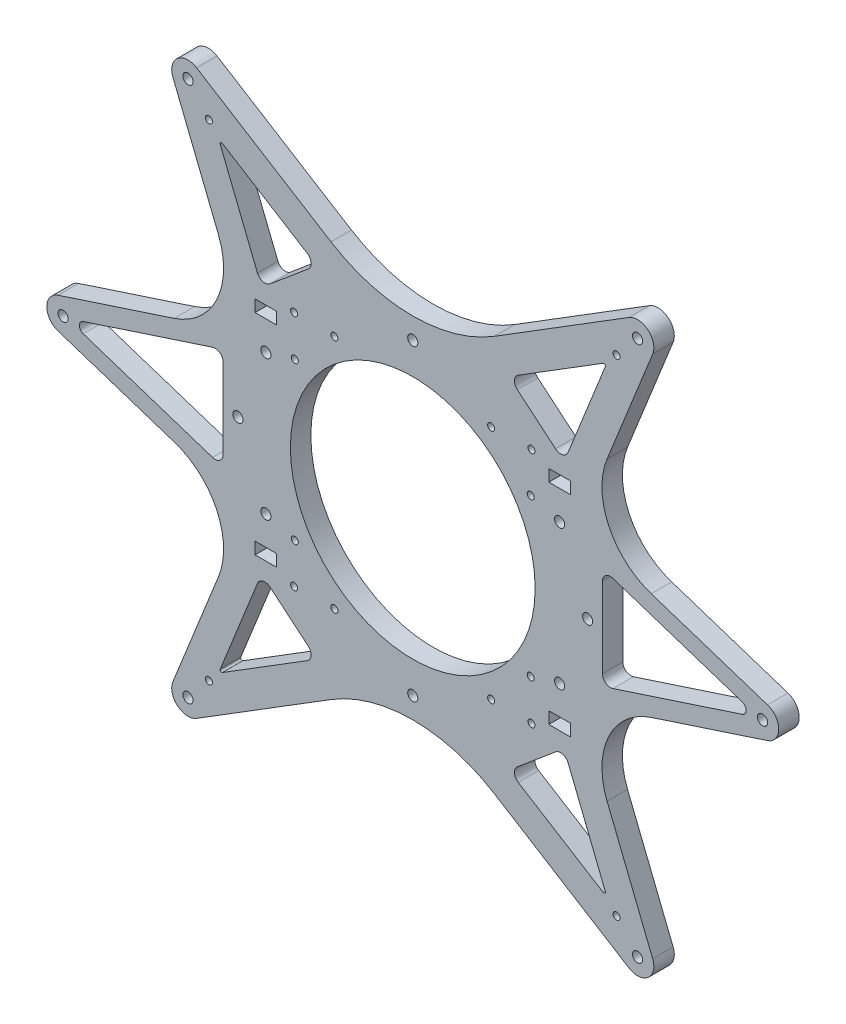
SolidWorks part; units mm, degrees
material "Acrylic (Medium-high impact)"
ref_plane "Front Plane" through (0, 0, 0) normal (0, 0, 1) x (1, 0, 0)
ref_plane "Top Plane" through (0, 0, 0) normal (0, 1, 0) x (1, 0, 0)
ref_plane "Right Plane" through (0, 0, 0) normal (1, 0, 0) x (0, 0, -1)
sketch "Sketch1" plane through (0, 0, 0) normal (0, 0, 1) x (1, 0, 0)
  line L0 (-447622.4345, 422.8828) -> (448935.6268, 422.8828) construction
  line L1 (587.9953, 497.7534) -> (601.0264, 465.2697)
  line L2 (698.5962, 452.8828) -> (698.5962, 392.8828) construction
  line L3 (653.3971, 419.0702) -> (-31485.9834, -37883.1519) construction
  line L4 (701.6962, 394.5828) -> (695.4962, 391.1828) construction
  line L5 (701.6962, 391.1828) -> (695.4962, 394.5828) construction
  line L6 (626.4541, 473.2977) -> (602.1777, 488.3841)
  line L7 (594.7755, 503.4426) -> (633.2109, 479.5572)
  line L8 (601.5396, 487.8487) -> (612.1813, 461.3214)
  line L9 (598.3082, 492.3477) -> (598.7333, 491.841) construction
  line L10 (701.6962, 391.1828) -> (695.4962, 391.1828)
  line L11 (695.4962, 394.5828) -> (695.4962, 391.1828)
  line L12 (701.6962, 394.5828) -> (695.4962, 394.5828)
  line L13 (594.7755, 503.4426) -> (587.9953, 497.7534) construction
  line L14 (626.7171, 469.6022) -> (615.775, 460.4206)
  line L15 (686.4752, 469.6022) -> (697.4174, 460.4206)
  line L16 (701.6962, 394.5828) -> (701.6962, 391.1828)
  line L17 (-343.4038, 422.8828) -> (49656.5962, 422.8828) construction
  line L18 (648.8948, 432.061) -> (-31490.4849, 38734.2822) construction
  line L19 (-347.3366, 472.8828) -> (49652.6634, 472.8828) construction
  line L20 (-347.2527, 372.8828) -> (49652.7473, 372.8828) construction
  line L21 (562.3601, 421.3552) -> (599.3601, 409.2322)
  line L22 (602.3601, 434.3594) -> (602.3601, 411.4062)
  line L23 (555.1462, 427.3082) -> (555.1462, 418.4573) construction
  line L24 (562.3601, 424.4103) -> (599.3601, 436.5334)
  line L25 (599.3601, 409.2322) -> (599.3601, 436.5334) construction
  line L26 (555.1462, 427.3082) -> (588.4064, 438.2059)
  line L27 (562.3601, 421.3552) -> (562.3601, 424.4103) construction
  line L28 (555.1462, 418.4573) -> (588.4064, 407.5596)
  line L29 (686.7382, 473.2977) -> (711.0147, 488.3841)
  line L30 (594.7755, 342.3229) -> (633.2109, 366.2084)
  line L31 (711.6527, 487.8487) -> (701.0111, 461.3214)
  line L32 (611.4962, 451.1828) -> (617.6962, 454.5828) construction
  line L33 (611.4962, 454.5828) -> (617.6962, 451.1828) construction
  line L34 (601.5396, 357.9169) -> (612.1813, 384.4442)
  line L35 (587.9953, 348.0122) -> (594.7755, 342.3229) construction
  line L36 (626.4541, 372.4678) -> (602.1777, 357.3814)
  line L37 (626.7171, 376.1634) -> (615.775, 385.3449)
  line L38 (587.9953, 348.0122) -> (601.0264, 380.4959)
  line L39 (611.4962, 391.1828) -> (617.6962, 394.5828) construction
  line L40 (701.6962, 454.5828) -> (695.4962, 451.1828) construction
  line L41 (611.4962, 394.5828) -> (617.6962, 391.1828) construction
  line L42 (614.5962, 452.8828) -> (614.5962, 392.8828) construction
  line L43 (701.6962, 451.1828) -> (695.4962, 454.5828) construction
  line L44 (686.4752, 376.1634) -> (697.4174, 385.3449)
  line L45 (725.1971, 348.0122) -> (718.4169, 342.3229) construction
  line L46 (711.6527, 357.9169) -> (701.0111, 384.4442)
  line L47 (750.8323, 421.3552) -> (750.8323, 424.4103) construction
  line L48 (713.8323, 409.2322) -> (713.8323, 436.5334) construction
  line L49 (758.0462, 427.3082) -> (758.0462, 418.4573) construction
  line L50 (686.7382, 372.4678) -> (711.0147, 357.3814)
  line L51 (718.4169, 503.4426) -> (725.1971, 497.7534) construction
  line L53 (611.4962, 454.5828) -> (617.6962, 454.5828)
  line L54 (617.6962, 451.1828) -> (617.6962, 454.5828)
  line L55 (611.4962, 451.1828) -> (617.6962, 451.1828)
  line L56 (701.6962, 451.1828) -> (701.6962, 454.5828)
  line L57 (701.6962, 451.1828) -> (695.4962, 451.1828)
  line L58 (695.4962, 451.1828) -> (695.4962, 454.5828)
  line L59 (701.6962, 454.5828) -> (695.4962, 454.5828)
  line L60 (725.1971, 348.0122) -> (712.166, 380.4959)
  line L63 (718.4169, 342.3229) -> (679.9814, 366.2084)
  line L65 (758.0462, 418.4573) -> (724.786, 407.5596)
  line L66 (758.0462, 427.3082) -> (724.786, 438.2059)
  line L67 (750.8323, 424.4103) -> (713.8323, 436.5334)
  line L68 (710.8323, 434.3594) -> (710.8323, 411.4062)
  line L69 (750.8323, 421.3552) -> (713.8323, 409.2322)
  line L70 (611.4962, 451.1828) -> (611.4962, 454.5828)
  line L72 (611.4962, 394.5828) -> (611.4962, 391.1828)
  line L73 (611.4962, 394.5828) -> (617.6962, 394.5828)
  line L74 (617.6962, 394.5828) -> (617.6962, 391.1828)
  line L76 (718.4169, 503.4426) -> (679.9814, 479.5572)
  line L78 (725.1971, 497.7534) -> (712.166, 465.2697)
  line L79 (611.4962, 391.1828) -> (617.6962, 391.1828)
  line L80 (706.5962, 432.8828) -> (698.5962, 432.8828) construction
  line L82 (656.5962, 378.8828) -> (646.5962, 378.8828) construction
  line L83 (656.5962, 466.8828) -> (646.5962, 466.8828) construction
  line L84 (-50.5106, -284.224) -> (35304.8285, 35071.1151) construction
  line L85 (-50.5106, -284.224) -> (35304.8285, 35071.1151) construction
  line L86 (1363.703, -284.224) -> (-33991.6361, 35071.1151) construction
  line L91 (598.3082, 492.3477) -> (595.2884, 495.9465) construction
  line L92 (592.3174, 499.4872) -> (598.3082, 492.3477) construction
  line L111 (656.5962, -513.6368) -> (656.5962, 49486.3632) construction
  arc A0 (601.5396, 487.8487) -> (602.1777, 488.3841) centre (601.9464, 488.0119) cw
  arc A1 (587.9953, 497.7534) -> (594.7755, 503.4426) centre (592.3174, 499.4872) cw
  circle A2 centre (592.3174, 499.4872) radius 1.45
  arc A4 (612.1813, 461.3214) -> (615.775, 460.4206) centre (614.3045, 462.1731) ccw
  arc A5 (626.4541, 473.2977) -> (626.7171, 469.6022) centre (625.2466, 471.3546) cw
  circle A6 centre (592.3174, 499.4872) radius 4.6569 construction
  circle A7 centre (622.6551, 456.8239) radius 1
  circle A8 centre (614.5962, 442.8828) radius 1.45
  circle A9 centre (690.5373, 456.8239) radius 1
  circle A10 centre (679.0129, 456.6132) radius 1
  arc A11 (555.1462, 418.4573) -> (555.1462, 427.3082) centre (556.5962, 422.8828) cw
  circle A12 centre (556.5962, 422.8828) radius 1.45
  circle A13 centre (690.3266, 445.2995) radius 1
  circle A14 centre (556.5962, 422.8828) radius 4.6569 construction
  arc A15 (562.3601, 424.4103) -> (562.3601, 421.3552) centre (562.8606, 422.8828) ccw
  circle A16 centre (656.5962, 422.8828) radius 35
  arc A18 (711.6527, 487.8487) -> (711.0147, 488.3841) centre (711.246, 488.0119) ccw
  arc A19 (602.3601, 434.3594) -> (599.3601, 436.5334) centre (600.0724, 434.3594) ccw
  arc A20 (686.7382, 473.2977) -> (686.4752, 469.6022) centre (687.9457, 471.3546) ccw
  arc A21 (599.3601, 409.2322) -> (602.3601, 411.4062) centre (600.0724, 411.4062) ccw
  circle A22 centre (656.5962, 466.8828) radius 1.45
  arc A23 (701.0111, 461.3214) -> (697.4174, 460.4206) centre (698.8879, 462.1731) cw
  circle A24 centre (592.3174, 346.2783) radius 4.6569 construction
  circle A25 centre (714.8842, 492.3477) radius 1
  arc A27 (594.7755, 342.3229) -> (587.9953, 348.0122) centre (592.3174, 346.2783) cw
  circle A28 centre (634.1795, 389.1524) radius 1
  circle A29 centre (622.6551, 388.9417) radius 1
  circle A31 centre (592.3174, 346.2783) radius 1.45
  circle A32 centre (622.8658, 400.4661) radius 1
  arc A33 (588.4064, 407.5596) -> (601.0264, 380.4959) centre (582.0351, 388.1144) cw
  circle A34 centre (656.5962, 378.8828) radius 1.45
  arc A35 (588.4064, 438.2059) -> (601.0264, 465.2697) centre (582.0351, 457.6512) ccw
  circle A37 centre (698.5962, 442.8828) radius 1.45
  circle A38 centre (698.5962, 402.8828) radius 1.45
  arc A39 (633.2109, 366.2084) -> (656.5962, 372.8828) centre (656.5962, 328.5778) cw
  arc A40 (633.2109, 479.5572) -> (656.5962, 472.8828) centre (656.5962, 517.1878) ccw
  circle A41 centre (720.8749, 346.2783) radius 4.6569 construction
  circle A42 centre (756.5962, 422.8828) radius 4.6569 construction
  circle A43 centre (598.3082, 353.4179) radius 1
  circle A44 centre (622.8658, 445.2995) radius 1
  circle A45 centre (634.1795, 456.6132) radius 1
  circle A46 centre (720.8749, 499.4872) radius 4.6569 construction
  circle A47 centre (598.3082, 492.3477) radius 1
  arc A48 (601.5396, 357.9169) -> (602.1777, 357.3814) centre (601.9464, 357.7537) ccw
  arc A49 (626.4541, 372.4678) -> (626.7171, 376.1634) centre (625.2466, 374.4109) ccw
  circle A50 centre (706.5962, 422.8828) radius 1.45
  arc A51 (679.9814, 479.5572) -> (656.5962, 472.8828) centre (656.5962, 517.1878) cw
  arc A52 (679.9814, 366.2084) -> (656.5962, 372.8828) centre (656.5962, 328.5778) ccw
  arc A53 (612.1813, 384.4442) -> (615.775, 385.3449) centre (614.3045, 383.5924) cw
  circle A54 centre (679.0129, 389.1524) radius 1
  arc A55 (724.786, 438.2059) -> (712.166, 465.2697) centre (731.1572, 457.6512) cw
  arc A56 (724.786, 407.5596) -> (712.166, 380.4959) centre (731.1572, 388.1144) ccw
  circle A57 centre (690.5373, 388.9417) radius 1
  circle A58 centre (720.8749, 346.2783) radius 1.45
  circle A59 centre (690.3266, 400.4661) radius 1
  circle A60 centre (714.8842, 353.4179) radius 1
  arc A61 (718.4169, 342.3229) -> (725.1971, 348.0122) centre (720.8749, 346.2783) ccw
  arc A62 (711.6527, 357.9169) -> (711.0147, 357.3814) centre (711.246, 357.7537) cw
  arc A63 (713.8323, 409.2322) -> (710.8323, 411.4062) centre (713.12, 411.4062) cw
  arc A64 (710.8323, 434.3594) -> (713.8323, 436.5334) centre (713.12, 434.3594) cw
  arc A65 (701.0111, 384.4442) -> (697.4174, 385.3449) centre (698.8879, 383.5924) ccw
  arc A66 (750.8323, 424.4103) -> (750.8323, 421.3552) centre (750.3318, 422.8828) cw
  arc A67 (686.7382, 372.4678) -> (686.4752, 376.1634) centre (687.9457, 374.4109) cw
  circle A68 centre (756.5962, 422.8828) radius 1.45
  arc A69 (758.0462, 418.4573) -> (758.0462, 427.3082) centre (756.5962, 422.8828) ccw
  circle A71 centre (606.5962, 422.8828) radius 1.45
  circle A76 centre (720.8749, 499.4872) radius 1.45
  arc A77 (725.1971, 497.7534) -> (718.4169, 503.4426) centre (720.8749, 499.4872) ccw
  circle A79 centre (614.5962, 402.8828) radius 1.45
  point P2 (621.2461, 465.0114)
  point P4 (604.6798, 472.924)
  point P5 (610.6788, 407.5004)
  point P6 (604.4937, 430.5743)
  point P7 (590.1096, 382.987)
  point P9 (656.5962, 422.8828)
  point P10 (592.2236, 451.9603)
  point P12 (560.2236, 451.9603)
  point P13 (615.5787, 412.0526)
  point P15 (596.4648, 452.5325)
  point P16 (593.7956, 519.1439)
  point P18 (562.0153, 451.7438)
  point P19 (589.324, 503.0546)
  point P21 (557.1601, 445.912)
  point P22 (691.7574, 496.0365)
  point P23 (586.2073, 519.1355)
  point P25 (698.5962, 452.8828)
  point P27 (593.4054, 384.161)
  point P31 (706.9167, 384.1702)
  point P32 (709.3005, 386.1481)
  point P33 (712.3266, 520.5499)
  point P34 (710.2125, 451.5766)
  point P37 (593.7956, 519.1439)
  point P38 (704.5328, 382.1922)
  point P40 (675.1867, 401.4708)
  point P41 (685.2778, 409.8289)
  point P43 (705.5495, 376.706)
  point P44 (637.2651, 404.097)
  point P46 (743.1543, 445.9191)
  point P47 (656.5962, 422.8828)
  point P48 (685.1467, 493.2598)
  point P49 (742.2125, 451.5766)
  point P53 (695.1768, 484.8286)
  point P55 (708.8884, 517.1528)
  point P56 (706.5155, 519.1439)
  point P57 (714.1038, 519.1355)
  point P64 (708.6406, 384.393)
  point P66 (665.171, 499.4399)
  point P67 (704.1427, 521.135)
  point P80 (602.3601, 422.8828)
  point P86 (499.5503, 435.3778)
  point P114 (563.3616, 328.8714)
  point P127 (698.5962, 422.8828)
  point P132 (656.5962, 457.8828)
  point P136 (656.5962, 465.4328)
  point P143 (704.687, 438.4721)
  point P145 (738.2906, 448.6533)
  point P146 (704.7346, 451.575)
  point P147 (738.2991, 451.7509)
  point P148 (738.3077, 454.8484)
  point P244 (749.8308, 328.8714)
  point P246 (710.8323, 422.8828)
  point P247 (698.5962, 422.8828)
  point P248 (723.8684, 503.0546)
  dimension "D2" = 2.9
  dimension "D6" = 8
  dimension "D9" = 48
  dimension "D7" = 8
  dimension "D11" = 100
  dimension "D12" = 9.32
  dimension "D5" = 10
  dimension "D19" = 50
  dimension "D20" = 100
  dimension "D25" = 6.2644
  dimension "D15" = 5.66
  dimension "D18" = 42
  dimension "D23" = 10
  dimension "D28" = 10
  dimension "D39" = 3.4
  dimension "D37" = 2.9
  dimension "D38" = 70
  dimension "D40" = 7.55
  dimension "D8" = 50
  dimension "D10" = 30
  dimension "D14" = 50
  dimension "D16" = 37
  dimension "D21" = 44
  dimension "D22" = 35
  dimension "D24" = 5
  dimension "D26" = 3
  dimension "D27" = 8
  dimension "D34" = 100
  dimension "D41" = 6.2
  dimension "D43" = 40.5
  dimension "D44" = 40.5
extrude "Boss-Extrude1" add sketch "Sketch1" along normal blind 5.85
